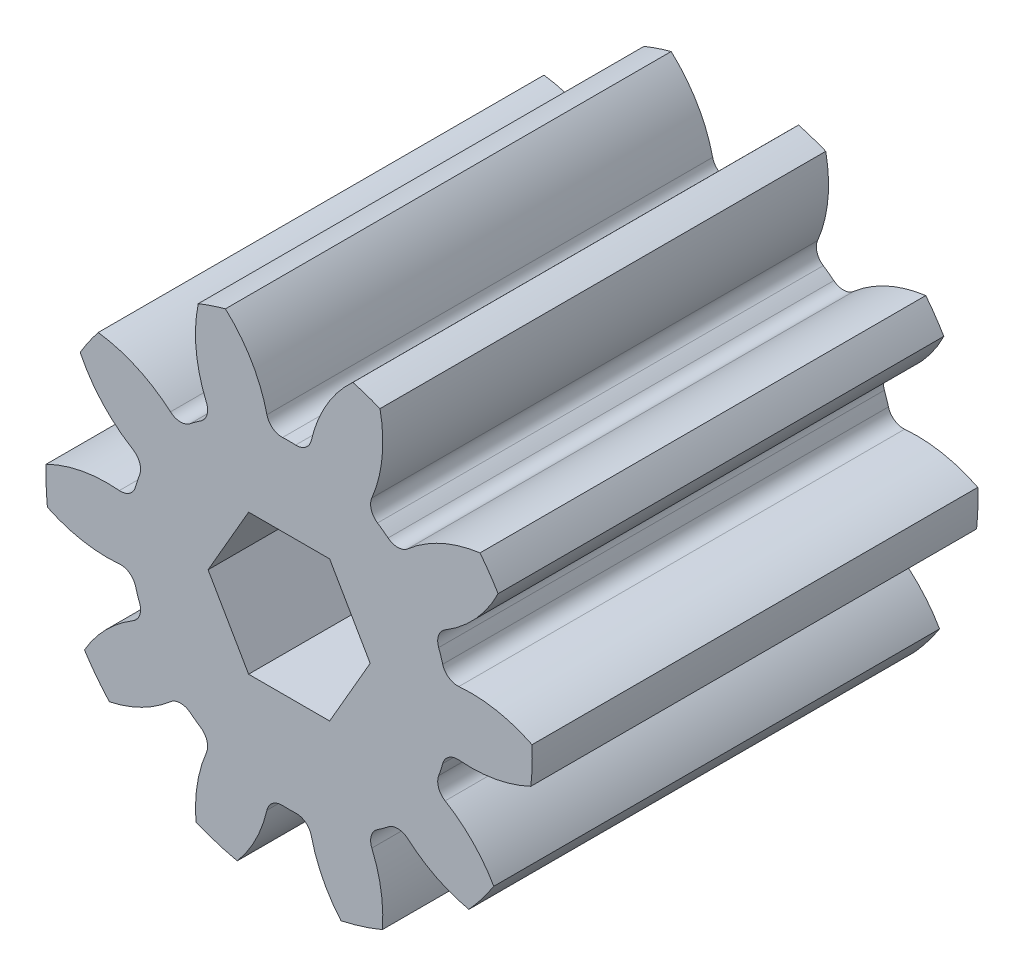
SolidWorks part; units mm, degrees
note: The reader was unsure of these and kept them because the rebuilt part matched: shared geometry of "Sketch1<4>".
ref_plane "Front Plane" through (0, 0, 0) normal (0, 0, 1) x (1, 0, 0)
ref_plane "Top Plane" through (0, 0, 0) normal (0, 1, 0) x (1, 0, 0)
ref_plane "Right Plane" through (0, 0, 0) normal (1, 0, 0) x (0, 0, -1)
sketch "Sketch1" plane through (0, 0, 0) normal (0, 0, 1) x (1, 0, 0)
  line L4 (-0.4895, 3.7179) -> (0, 0) construction
  line L5 (0, 0) -> (0, 6) construction
  line L7 (-0.8854, 4.921) -> (1.3694, 6.2333) construction
  line L8 (-0.8854, 4.921) -> (1.1078, 5.2796) construction
  line L11 (0.8854, 4.921) -> (-0.8854, 4.921) construction
  circle A0 centre (0, 0) radius 3.75
  circle A1 centre (0, 0) radius 5 construction
  circle A2 centre (0, 0) radius 6
  arc A3 (-1.5719, 5.7904) -> (-0.4895, 3.7179) centre (-3.866, 3.2734) cw
  arc A4 (1.5719, 5.7904) -> (0.4895, 3.7179) centre (3.866, 3.2734) ccw
  point P5 (-5, 0)
  point P6 (-6, 0)
  point P7 (-3.75, 0)
  point P12 (-0.8854, 4.921)
  point P22 (0.8854, 4.921)
  dimension "D5" = 10
  dimension "D8" = 3.4057
  dimension "D1" = 1.25
  dimension "D2" = 1
  dimension "D3" = 20
  dimension "D4" = 1.7708
  dimension "D6" = 7.5
  dimension "D7" = 0.9789
extrude "Boss-Extrude1" add sketch "Sketch1" against normal blind 11 contours A2
extrude "Cut-Extrude1" cut sketch "Sketch1<4>" against normal blind 11 contours A4 A2 A3 A0
sketch "Sketch1<4>" plane through (0, 0, 0) normal (0, 0, 1) x (1, 0, 0) same geometry as "Sketch1"
fillet "Fillet2" radius 0.38 2 edges at (0.4895, 3.7179, -5.5) (-0.4895, 3.7179, -5.5)
pattern_circular "CirPattern2" count 10 over 360 about axis through (0, -0.1862, 0) along (0, 0, 1) of "Cut-Extrude1", "Fillet2"
sketch "Sketch2" plane through (0, 0, 0) normal (0, 0, 1) x (1, 0, 0)
  line L1 (-1, 1.7321) -> (-2, 0)
  line L2 (-2, 0) -> (-1, -1.7321)
  line L3 (-1, -1.7321) -> (1, -1.7321)
  line L4 (1, -1.7321) -> (2, 0)
  line L5 (2, 0) -> (1, 1.7321)
  line L6 (1, 1.7321) -> (-1, 1.7321)
  circle A0 centre (0, 0) radius 1.7321 construction
  dimension "D1" = 2
extrude "Cut-Extrude2" cut sketch "Sketch2" against normal through all
equation "\"backlash\"= 0.2mm"
equation "\"module\"= 1mm"
equation "\"pressureAngle\"= 20deg"
equation "\"numberOfTeethRack\"= 12"
equation "\"lengthOverallRack\"= pi * \"module\" * \"numberOfTeethRack\""
equation "\"backThickness\"= 6mm"
equation "\"width\" = 8mm"
equation "\"D1@Sketch1\"= 1.25 * \"module\""
equation "\"D2@Sketch1\"=\"module\""
equation "\"D5@Sketch1\"=\"module\"*\"numberOfTeethPinion\""
equation "\"numberOfTeethPinion\"= 10"
equation "\"D1@Boss-Extrude1\"=\"width\"+3"
equation "\"D3@Sketch1\"=\"pressureAngle\""
equation "\"D1@Cut-Extrude1\"=\"width\"+3"
equation "\"D1@CirPattern2\"=\"numberOfTeethPinion\""
equation "\"D1@Fillet2\"=0.38*\"module\""
equation "\"D4@Sketch1\"=pi*\"module\"/2+\"backlash\""
